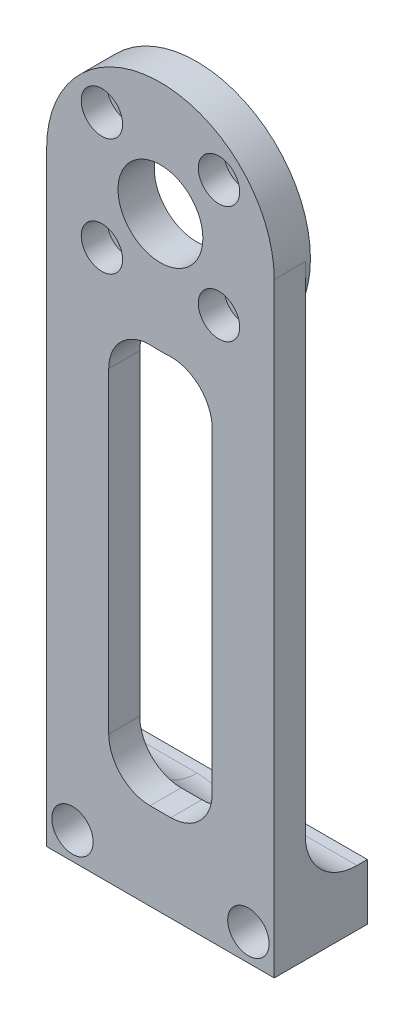
SolidWorks part; units mm, degrees
ref_plane "Front Plane" through (0, 0, 0) normal (0, 0, 1) x (1, 0, 0)
ref_plane "Top Plane" through (0, 0, 0) normal (0, 1, 0) x (1, 0, 0)
ref_plane "Right Plane" through (0, 0, 0) normal (1, 0, 0) x (0, 0, -1)
sketch "Sketch1" plane through (0, 0, 0) normal (0, 0, 1) x (1, 0, 0)
  line L0 (0, 29.235) -> (0, -29.235) construction
  line L2 (11, 29.235) -> (11, -29.235)
  line L4 (-11, 29.235) -> (-11, -29.235)
  line L5 (-11, -29.235) -> (11, -29.235)
  line L7 (11, -29.235) -> (-11, -29.235)
  line L8 (11, -29.235) -> (11, -23.815)
  line L9 (11, -23.815) -> (-11, -23.815)
  line L10 (-11, -29.235) -> (-11, -23.815)
  line L12 (-5, 18.8788) -> (-5, -20.815)
  line L13 (-5, -20.815) -> (5, -20.815)
  line L14 (5, 18.8788) -> (5, -20.815)
  circle A0 centre (0, 29.235) radius 11
  arc A1 (-5, 18.8788) -> (5, 18.8788) centre (0, 29.235) ccw
  point P0 (0, 0)
  point P2 (0, 0)
  point P8 (0, -29.235)
  dimension "D3" = 22
  dimension "D1" = 58.47
  dimension "D4" = 5.42
  dimension "D5" = 23
  dimension "D7" = 6
  dimension "D2" = 22
  dimension "D6" = 3
  dimension "D8" = 6
extrude "Boss-Extrude1" add sketch "Sketch1" along normal blind 3 contours L2 A0 L4 | A0 | A0 L0 L2 | L8 L7 L10 L9 region at (0, 29.235, 0) region at (10.4257, 2.71, 0)
extrude "Boss-Extrude2" add sketch "Sketch1<3>" against normal blind 0.5 contours A0 region at (0, 29.235, 0)
sketch "Sketch1<3>" plane through (0, 0, 0) normal (0, 0, 1) x (1, 0, 0) same geometry as "Sketch1"
sketch "Sketch2" plane through (0, 0, 3) normal (0, 0, 1) x (1, 0, 0)
  line L0 (0, 29.235) -> (5.6569, 34.8919) construction
  line L1 (11, 29.235) -> (11, -29.235) construction
  circle A0 centre (0, 29.235) radius 4.1
  circle A1 centre (5.6569, 34.8919) radius 1.1
  circle A2 centre (5.6569, 34.8919) radius 2
  dimension "D1" = 8.2
  dimension "D2" = 2.2
  dimension "D5" = 4
  dimension "D3" = 8
  dimension "D4" = 45
extrude "Cut-Extrude1" cut sketch "Sketch2" against normal up to surface (3.5 mm away) contours A0 | A1 region at (0, 29.235, 3) region at (5.6569, 34.8919, 3) up to face at (11, 29.235, -0.5)
extrude "Cut-Extrude2" cut sketch "Sketch2<3>" against normal offset from surface (2.5 mm away) 1 contours A2 A1 region at (3.7134, 34.8919, 3) up to face at (4.1, 29.235, -0.5)
sketch "Sketch2<3>" plane through (0, 0, 3) normal (0, 0, 1) x (1, 0, 0) same geometry as "Sketch2"
pattern_circular "CirPattern2" count 4 over 360 about axis through (0, 29.235, 3) along (0, 0, 1) of "Cut-Extrude2", "Cut-Extrude1"
extrude "Boss-Extrude3" add sketch "Sketch1<6>" against normal blind 6 contours L0 L9 L4 L5 | L9 L0 L7 L2 region at (-5.5, -26.525, 0) region at (5.5, -26.525, 0)
sketch "Sketch1<6>" plane through (0, 0, 0) normal (0, 0, 1) x (1, 0, 0) same geometry as "Sketch1"
sketch "Sketch3" plane through (0, 0, 3) normal (0, 0, 1) x (1, 0, 0)
  line L0 (-8.5, -26.6202) -> (8.5, -26.6202) construction
  line L1 (-11, -29.235) -> (11, -29.235) construction
  circle A0 centre (-8.5, -26.6202) radius 1.1
  circle A1 centre (8.5, -26.6202) radius 1.1
  circle A2 centre (-8.5, -26.6202) radius 2
  circle A3 centre (8.5, -26.6202) radius 2
  point P4 (0, -26.6202)
  dimension "D1" = 2.2
  dimension "D4" = 4
  dimension "D2" = 17
  dimension "D3" = 2.6148
extrude "Cut-Extrude3" cut sketch "Sketch3" against normal up to surface (9 mm away) contours A0 | A1 region at (-8.5, -26.6202, 3) region at (8.5, -26.6202, 3) up to face at (0, -26.525, -6)
extrude "Cut-Extrude4" cut sketch "Sketch3<3>" against normal offset from surface (8 mm away) 1 up to face at (-7.4, -26.6202, -6)
sketch "Sketch3<3>" plane through (0, 0, 3) normal (0, 0, 1) x (1, 0, 0) same geometry as "Sketch3"
fillet "Filete1" radius 4 4 edges at (5, 18.8788, 1.5) (-5, 18.8788, 1.5) (5, -20.815, 1.5) (-5, -20.815, 1.5)
fillet "Filete3" radius 5 1 edges at (0, -23.815, 0)
